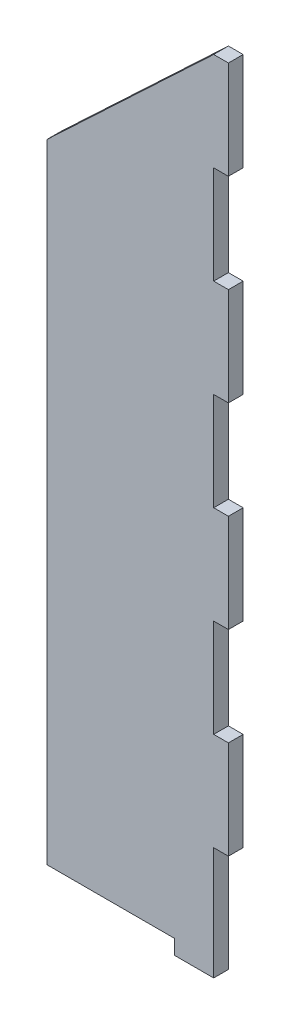
SolidWorks part; units mm, degrees
ref_plane "Front Plane" through (0, 0, 0) normal (0, 0, 1) x (1, 0, 0)
ref_plane "Top Plane" through (0, 0, 0) normal (0, 1, 0) x (1, 0, 0)
ref_plane "Right Plane" through (0, 0, 0) normal (1, 0, 0) x (0, 0, -1)
sketch "Sketch1" plane through (0, 0, 0) normal (0, 0, 1) x (1, 0, 0)
  line L0 (-26.9875, -101.6) -> (-26.9875, 101.6)
  line L1 (-26.9875, 101.6) -> (26.9875, 152.4)
  line L2 (26.9875, 152.4) -> (26.9875, -101.6)
  line L3 (26.9875, -101.6) -> (-26.9875, -101.6)
  line L4 (-26.9875, 0) -> (26.9875, 0) construction
  line L5 (26.9875, 120.65) -> (26.9875, 88.9)
  line L6 (26.9875, 152.4) -> (31.75, 152.4)
  line L7 (26.9875, 152.4) -> (26.9875, 120.65)
  line L8 (26.9875, 120.65) -> (31.75, 120.65)
  line L9 (31.75, 152.4) -> (31.75, 120.65)
  line L10 (26.9875, 120.65) -> (31.75, 120.65)
  line L11 (31.75, 120.65) -> (31.75, 88.9)
  line L12 (26.9875, 88.9) -> (31.75, 88.9)
  line L13 (26.9875, 88.9) -> (26.9875, 57.15)
  line L14 (26.9875, 88.9) -> (31.75, 88.9)
  line L15 (31.75, 88.9) -> (31.75, 57.15)
  line L16 (26.9875, 57.15) -> (31.75, 57.15)
  line L17 (26.9875, 57.15) -> (26.9875, 25.4)
  line L18 (26.9875, 57.15) -> (31.75, 57.15)
  line L19 (31.75, 57.15) -> (31.75, 25.4)
  line L20 (26.9875, 25.4) -> (31.75, 25.4)
  line L21 (26.9875, 25.4) -> (26.9875, -6.35)
  line L22 (26.9875, 25.4) -> (31.75, 25.4)
  line L23 (31.75, 25.4) -> (31.75, -6.35)
  line L24 (26.9875, -6.35) -> (31.75, -6.35)
  line L25 (26.9875, -6.35) -> (26.9875, -38.1)
  line L26 (26.9875, -6.35) -> (31.75, -6.35)
  line L27 (31.75, -6.35) -> (31.75, -38.1)
  line L28 (26.9875, -38.1) -> (31.75, -38.1)
  line L29 (26.9875, -38.1) -> (26.9875, -69.85)
  line L30 (26.9875, -38.1) -> (31.75, -38.1)
  line L31 (31.75, -38.1) -> (31.75, -69.85)
  line L32 (26.9875, -69.85) -> (31.75, -69.85)
  line L33 (26.9875, -69.85) -> (26.9875, -101.6)
  line L42 (26.9875, -69.85) -> (31.75, -69.85)
  line L43 (31.75, -69.85) -> (31.75, -101.6)
  line L44 (26.9875, -101.6) -> (31.75, -101.6)
  line L46 (14.2875, -101.6) -> (26.9875, -101.6)
  line L47 (14.2875, -101.6) -> (14.2875, -106.3625)
  line L48 (14.2875, -106.3625) -> (26.9875, -106.3625)
  line L49 (26.9875, -101.6) -> (26.9875, -106.3625)
  point P2 (0, 0)
  dimension "D1" = 53.975
  dimension "D2" = 254
  dimension "D3" = 203.2
  dimension "D4" = 4.7625
  dimension "D6" = 31.75
  dimension "D7" = 12.7
  dimension "D8" = 4.7625
  dimension "D5" = 8
extrude "Boss-Extrude1" add sketch "Sketch1" along normal blind 4.7625 contours L4 L0 L3 L2 L21 | L0 L4 L2 L1 | L9 L6 L2 L8 | L2 L16 L15 L12 | L2 L21 L24 L23 L20 | L2 L32 L31 L28 | L32 L3 L47 region at (0, -50.8, 0) region at (1.7992, 64.3467, 0) region at (20.6375, -103.9813, 0) region at (29.3688, 9.525, 0) region at (29.3688, 136.525, 0) region at (29.3688, -53.975, 0) region at (29.3688, 73.025, 0)
equation "\"Height\"= 12in"
equation "\"Depth\"= 7in"
equation "\"WallThickness\"= 0.1875in"
equation "\"FloorThickness\"= 0.1875in"
equation "\"D1@Sketch1\"=(\"Depth\"-2.75)/2"
equation "\"D4@Sketch1\"=\"WallThickness\""
equation "\"D6@Sketch1\"=\"D2@Sketch1\"/\"D5@Sketch1\""
equation "\"D8@Sketch1\"=\"FloorThickness\""
equation "\"D1@Boss-Extrude1\"=\"WallThickness\""
equation "\"Width\"= 30in"
